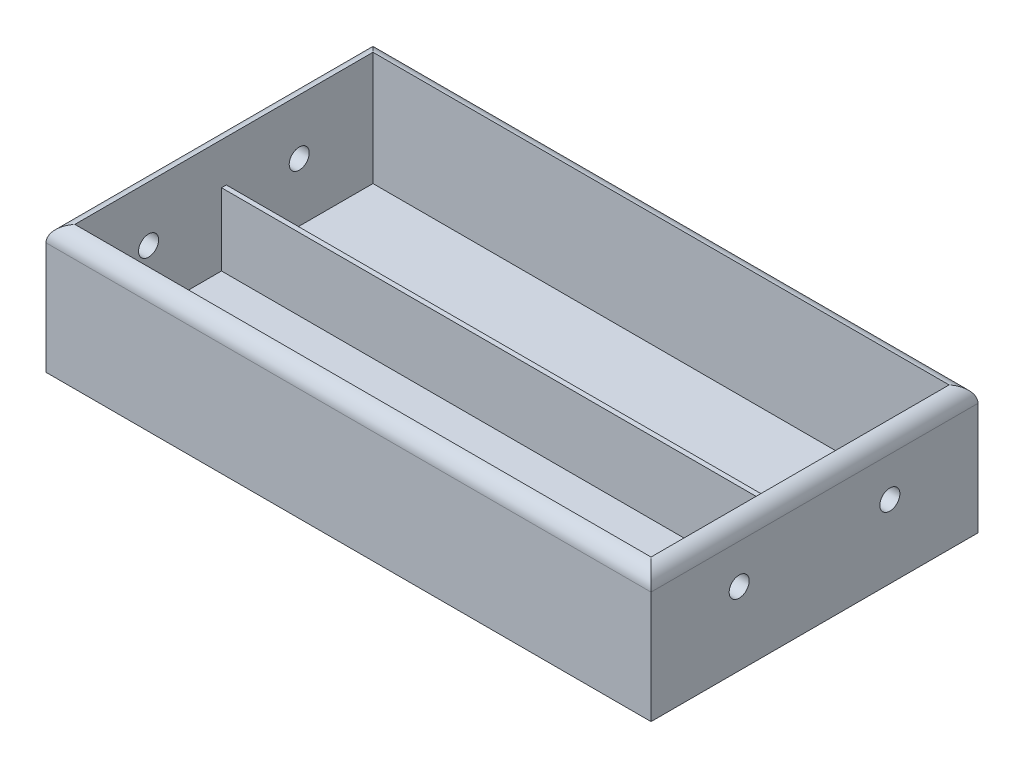
SolidWorks part; units mm, degrees
ref_plane "Alzado" through (0, 0, 0) normal (0, 0, 1) x (1, 0, 0)
ref_plane "Planta" through (0, 0, 0) normal (0, 1, 0) x (1, 0, 0)
ref_plane "Vista lateral" through (0, 0, 0) normal (1, 0, 0) x (0, 0, -1)
sketch "Croquis1" plane through (0, 0, 0) normal (0, 1, 0) x (1, 0, 0)
  line L1 (-37.75, 20.4) -> (37.75, 20.4)
  line L2 (-37.75, 20.4) -> (-37.75, -20.4)
  line L3 (-37.75, -20.4) -> (37.75, -20.4)
  line L4 (37.75, 20.4) -> (37.75, -20.4)
  line L5 (-37.75, 20.4) -> (37.75, -20.4) construction
  line L6 (-37.75, -20.4) -> (37.75, 20.4) construction
  point P1 (0, 0)
  dimension "D1" = 75.5
  dimension "D2" = 40.8
extrude "Saliente-Extruir1" add sketch "Croquis1" along normal blind 16
shell "Vaciado1" thickness 1.8 removed face at (0, 16, 0)
sketch "Croquis2" plane through (0, 0, 0) normal (0, 0, 1) x (1, 0, 0)
  line L0 (35.95, 1.8) -> (-35.95, 1.8) construction
  line L1 (35.95, 1.8) -> (-35.95, 1.8)
  line L2 (-35.95, 1.8) -> (-35.95, 10.8)
  line L3 (-35.95, 10.8) -> (35.95, 10.8)
  line L4 (35.95, 10.8) -> (35.95, 1.8)
  dimension "D1" = 9
extrude "Saliente-Extruir2" add sketch "Croquis2" along normal blind 0.3 and the other way blind 0.3
sketch "Croquis3" plane through (-37.75, 0, 0) normal (-1, 0, 0) x (0, 0, 1)
  circle A0 centre (9.4, 9.1) radius 1.25
  point P2 (3.2681, 8.4929)
  dimension "D1" = 2.5
  dimension "D2" = 9.4
  dimension "D3" = 9.1
extrude "Cortar-Extruir1" cut sketch "Croquis3" against normal up to surface (75.5 mm away) up to face at (37.75, 8, 0)
pattern_linear "MatrizL1" count 2 spacing 18.8 along (0, 0, -1) of "Cortar-Extruir1"
fillet "Redondeo1" radius 2 4 edges at (0, 16, -20.4) (-37.75, 16, 0) (0, 16, 20.4) (37.75, 16, 0)
